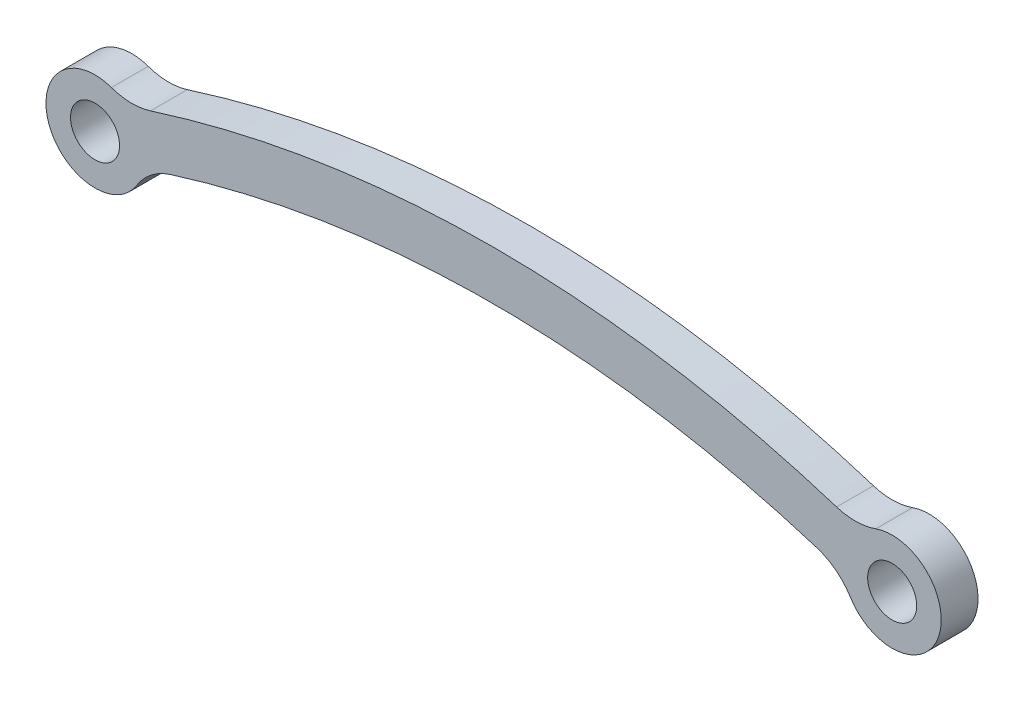
SolidWorks part; units mm, degrees
material "Thornel Mat VMA"
ref_plane "前视基准面" through (0, 0, 0) normal (0, 0, 1) x (1, 0, 0)
ref_plane "上视基准面" through (0, 0, 0) normal (0, 1, 0) x (1, 0, 0)
ref_plane "右视基准面" through (0, 0, 0) normal (1, 0, 0) x (0, 0, -1)
other "Configuration Table"
sketch "草图1" plane through (0, 0, 0) normal (0, 0, 1) x (1, 0, 0)
  line L0 (-65, 0) -> (65, 0) construction
  line L1 (-65, 4) -> (65, 4)
  line L2 (-65, -4) -> (65, -4)
  arc A0 (-65, 4) -> (-65, -4) centre (-65, 0) ccw
  arc A1 (65, -4) -> (65, 4) centre (65, 0) ccw
  circle A4 centre (-65, 0) radius 8
  circle A5 centre (65, 0) radius 8
  point P2 (0, 0)
  dimension "D3" = 16
  dimension "D1" = 130
  dimension "D2" = 8
extrude "凸台-拉伸1" add sketch "草图1" along normal blind 6 contours L1 A4 L2 A0 | L2 A4 L1 A0 | L0 A4 L2 A5 | A4 L0 A5 L1 | L1 A5 L2 A1 | L2 A5 L1 A1 region at (0, 2.0061, 0) region at (-57.4119, -2.0332, 0) region at (0, -2.0061, 0) region at (57.4119, 2.0332, 0) region at (-61.5359, 4.2188, 0) region at (67.0139, 7.516, 0)
sketch "草图2" plane through (0, 0, 6) normal (0, 0, 1) x (1, 0, 0)
  circle A0 centre (-65, 0) radius 4
  circle A1 centre (65, 0) radius 4
  dimension "D1" = 8
extrude "切除-拉伸1" cut sketch "草图2" against normal blind 15
fillet "圆角1" radius 10 4 edges at (58.0718, -4, 3) (-58.0718, -4, 3) (58.0718, 4, 3) (-58.0718, 4, 3)
sketch "草图4" plane through (0, 0, 6) normal (0, 0, 1) x (1, 0, 0)
  line L2 (-53.6863, -4) -> (53.6863, -4)
  line L3 (53.6863, 4) -> (-53.6863, 4)
  line L4 (-53.6863, -4) -> (53.6863, -4)
  line L5 (53.6863, 4) -> (-53.6863, 4)
  arc A0 (-65, 0) -> (65, 0) centre (0, -167.8541) cw
  arc A1 (-63.5556, -3.7301) -> (63.5556, -3.7301) centre (0, -167.8541) cw
  arc A2 (-66.4444, 3.7301) -> (66.4444, 3.7301) centre (0, -167.8541) cw
  arc A9 (59.9717, -6.2222) -> (53.6863, -4) centre (53.6863, -14) ccw
  arc A10 (59.9717, -6.2222) -> (59.9717, 6.2222) centre (65, 0) ccw
  arc A11 (53.6863, 4) -> (59.9717, 6.2222) centre (53.6863, 14) ccw
  arc A12 (-59.9717, 6.2222) -> (-53.6863, 4) centre (-53.6863, 14) ccw
  arc A13 (-59.9717, 6.2222) -> (-59.9717, -6.2222) centre (-65, 0) ccw
  arc A14 (-53.6863, -4) -> (-59.9717, -6.2222) centre (-53.6863, -14) ccw
  arc A15 (59.9717, -6.2222) -> (53.6863, -4) centre (53.6863, -14) ccw
  arc A16 (59.9717, -6.2222) -> (59.9717, 6.2222) centre (65, 0) ccw
  arc A17 (53.6863, 4) -> (59.9717, 6.2222) centre (53.6863, 14) ccw
  arc A18 (-59.9717, 6.2222) -> (-53.6863, 4) centre (-53.6863, 14) ccw
  arc A19 (-59.9717, 6.2222) -> (-59.9717, -6.2222) centre (-65, 0) ccw
  arc A20 (-53.6863, -4) -> (-59.9717, -6.2222) centre (-53.6863, -14) ccw
  point P11 (0, 0)
  arc M14 (59.9717, 6.2222) -> (53.6863, 4) centre (53.6863, 14) cw
  line M15 (53.6863, 4) -> (-53.6863, 4)
  arc M16 (-53.6863, 4) -> (-59.9717, 6.2222) centre (-53.6863, 14) cw
  dimension "D4" = 180
  dimension "D1" = 4
  dimension "D2" = 4
  dimension "D3" = 0
extrude "凸台-拉伸3" add sketch "草图4" against normal blind 6 contours L5 A1 A0 | A2 A0 M16 M15 M14 region at (0, 14.9425, 6) region at (0, 8.1683, 6)
sketch "草图5" plane through (0, 0, 6) normal (0, 0, 1) x (1, 0, 0)
  line L1 (-53.6863, -4) -> (53.6863, -4)
  line L2 (-53.6863, -4) -> (53.6863, -4)
  circle A0 centre (-65, 0) radius 8
  circle A1 centre (65, 0) radius 8
  circle A2 centre (0, -167.8541) radius 176
  arc A3 (37.9759, 4) -> (-37.9759, 4) centre (0, -167.8541) ccw construction
  arc A9 (59.9717, -6.2222) -> (53.6863, -4) centre (53.6863, -14) ccw
  arc A10 (59.9717, -6.2222) -> (59.9717, 6.2222) centre (65, 0) ccw
  arc A11 (59.863, 6.1356) -> (59.9717, 6.2222) centre (53.6863, 14) ccw
  arc A12 (59.863, 6.1356) -> (-59.863, 6.1356) centre (0, -167.8541) ccw
  arc A13 (-59.9717, 6.2222) -> (-59.863, 6.1356) centre (-53.6863, 14) ccw
  arc A14 (-59.9717, 6.2222) -> (-59.9717, -6.2222) centre (-65, 0) ccw
  arc A15 (-53.6863, -4) -> (-59.9717, -6.2222) centre (-53.6863, -14) ccw
  arc A16 (59.9717, -6.2222) -> (53.6863, -4) centre (53.6863, -14) ccw
  arc A17 (59.9717, -6.2222) -> (59.9717, 6.2222) centre (65, 0) ccw
  arc A18 (59.863, 6.1356) -> (59.9717, 6.2222) centre (53.6863, 14) ccw
  arc A19 (59.863, 6.1356) -> (-59.863, 6.1356) centre (0, -167.8541) ccw
  arc A20 (-59.9717, 6.2222) -> (-59.863, 6.1356) centre (-53.6863, 14) ccw
  arc A21 (-59.9717, 6.2222) -> (-59.9717, -6.2222) centre (-65, 0) ccw
  arc A22 (-53.6863, -4) -> (-59.9717, -6.2222) centre (-53.6863, -14) ccw
  line M11 (37.9759, 4) -> (-37.9759, 4)
  line M15 (-53.6863, -4) -> (53.6863, -4)
  arc M16 (53.6863, -4) -> (59.9717, -6.2222) centre (53.6863, -14) cw
  arc M22 (-59.9717, -6.2222) -> (-53.6863, -4) centre (-53.6863, -14) cw
  dimension "D1" = 16
  dimension "D2" = 0
extrude "切除-拉伸2" cut sketch "草图5" against normal blind 6 contours A1 A2 A0 M11 M22 M15 M16 region at (0, -0.2932, 6)
fillet "圆角2" radius 10 4 edges at (57.1201, -1.381, 3) (59.863, 6.1356, 3) (-59.863, 6.1356, 3) (-57.1201, -1.381, 3)
